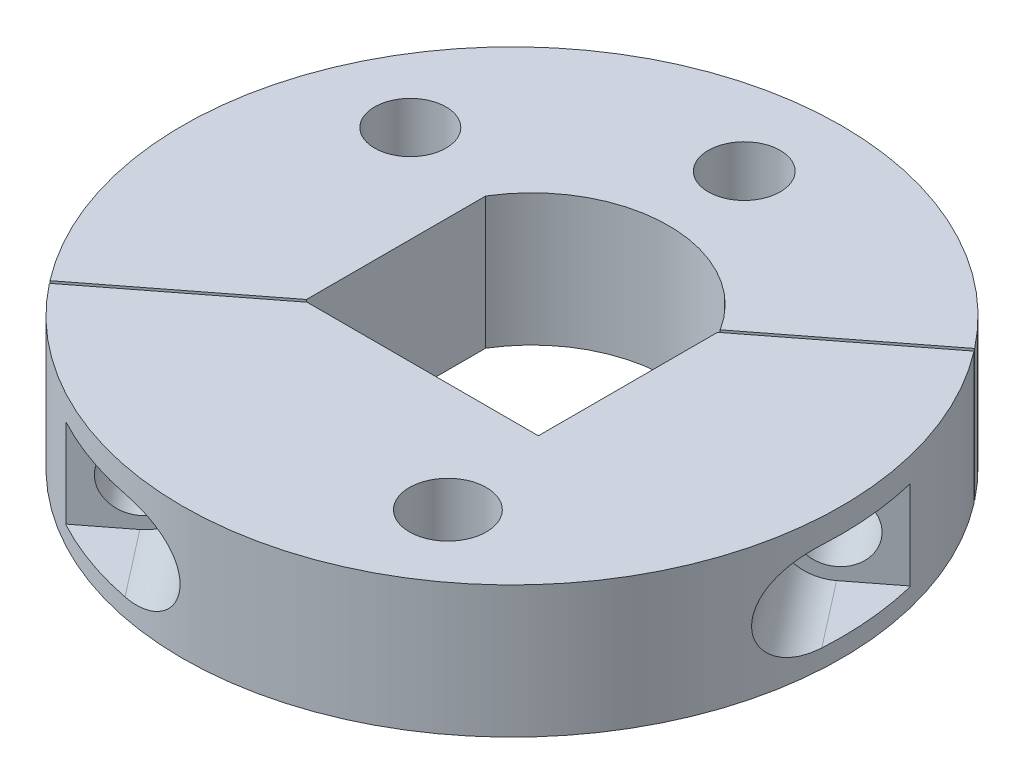
SolidWorks part; units mm, degrees
ref_plane "Front Plane" through (0, 0, 0) normal (0, 0, 1) x (1, 0, 0)
ref_plane "Top Plane" through (0, 0, 0) normal (0, 1, 0) x (1, 0, 0)
ref_plane "Right Plane" through (0, 0, 0) normal (1, 0, 0) x (0, 0, -1)
sketch "Sketch1" plane through (0, 0, 0) normal (0, 1, 0) x (1, 0, 0)
  circle A0 centre (0, 0) radius 25.4
  dimension "D1" = 50.8
extrude "Boss-Extrude1" add sketch "Sketch1" along normal blind 10.16
sketch "Sketch2" plane through (0, 10.16, 0) normal (0, 1, 0) x (1, 0, 0)
  line L1 (-9.017, -6.985) -> (9.017, -6.985)
  line L2 (-9.017, -6.985) -> (-9.017, 6.985)
  line L4 (9.017, -6.985) -> (9.017, 6.985)
  line L5 (-9.017, -6.985) -> (9.017, 6.985) construction
  line L6 (-9.017, 6.985) -> (9.017, -6.985) construction
  arc A0 (-9.017, 6.985) -> (9.017, 6.985) centre (0, 1.5224) cw
  point P0 (0, 0)
  point P7 (0, 12.065)
  dimension "D1" = 19.05
  dimension "D2" = 13.97
  dimension "D3" = 18.034
extrude "Cut-Extrude1" cut sketch "Sketch2" along direction (0, 1, 0) on the side against the normal through all
sketch "Sketch4" plane through (0, 10.16, 0) normal (0, 1, 0) x (1, 0, 0)
  line L0 (20.08, 15.5549) -> (-20.08, -15.5549) construction
  line L1 (20.0019, 15.6551) -> (-20.1575, -15.4543)
  line L2 (-20.0019, -15.6551) -> (20.1575, 15.4543)
  circle A0 centre (0, 0) radius 25.4 construction
  arc A1 (20.0019, 15.6551) -> (20.1575, 15.4543) centre (0, 0) cw
  arc A2 (-20.1575, -15.4543) -> (-20.0019, -15.6551) centre (0, 0) ccw
  dimension "D1" = 0.254
  dimension "D2" = 0.127
extrude "Cut-Extrude5" cut sketch "Sketch4" along direction (0, 1, 0) on the side against the normal through all
ref_plane "Plane1" through (6.2997, 0, 8.1324) normal (-0.6124, 0, -0.7905) x (-0.7905, 0, 0.6124)
sketch "Sketch5" plane through (6.2997, 0, 8.1324) normal (-0.6124, 0, -0.7905) x (-0.7905, 0, 0.6124)
  line L0 (0, -9.1397) -> (0, 24.4373) construction
  circle A0 centre (-19.1385, 4.8518) radius 2.5
  circle A2 centre (19.1385, 4.8518) radius 2.5
  dimension "D1" = 5
extrude "Cut-Extrude6" cut sketch "Sketch5" against normal through all both and the other way through all
sketch "Sketch6" plane through (6.2997, 0, 8.1324) normal (-0.6124, 0, -0.7905) x (-0.7905, 0, 0.6124)
  line L0 (-23.1915, 0) -> (-23.1915, 10.16) construction
  line L1 (25.3997, 10.16) -> (-25.3997, 10.16) construction
  line L2 (-25.3997, 0) -> (25.3997, 0) construction
  line L3 (-19.1385, 1.4115) -> (-23.1915, 1.4115)
  line L4 (-19.1385, 8.2921) -> (-23.1915, 8.2921)
  line L5 (0, -13.0186) -> (0, 31.6449) construction
  line L6 (-23.1915, 1.4115) -> (-23.1915, 8.2921)
  line L7 (23.1915, 0) -> (23.1915, 10.16) construction
  line L8 (19.1385, 1.4115) -> (23.1915, 1.4115)
  line L9 (23.1915, 1.4115) -> (23.1915, 8.2921)
  line L10 (19.1385, 8.2921) -> (23.1915, 8.2921)
  arc A0 (-19.1385, 1.4115) -> (-19.1385, 8.2921) centre (-19.1385, 4.8518) ccw
  arc A2 (19.1385, 1.4115) -> (19.1385, 8.2921) centre (19.1385, 4.8518) cw
extrude "Cut-Extrude7" cut sketch "Sketch6" against normal through all
sketch "Sketch3" plane through (0, 10.16, 0) normal (0, 1, 0) x (1, 0, 0)
  circle A0 centre (-16.4926, 8.6553) radius 2.7543
  circle A1 centre (-0.7132, 18.6122) radius 2.7743
  circle A3 centre (10.4662, -15.4072) radius 2.9677
  circle A4 centre (0, 0) radius 18.6258 construction
  point P4 (-16.6816, 8.7545)
  point P5 (-0.7188, 18.7574)
  point P11 (0, 0)
  point P12 (-3.917, -15.3855)
  point P13 (9.821, -16.0946)
  point P14 (12.2756, -12.962)
  point P15 (10.4662, -15.4072)
extrude "Cut-Extrude8" cut sketch "Sketch3" along direction (0, 1, 0) on the side against the normal through all
